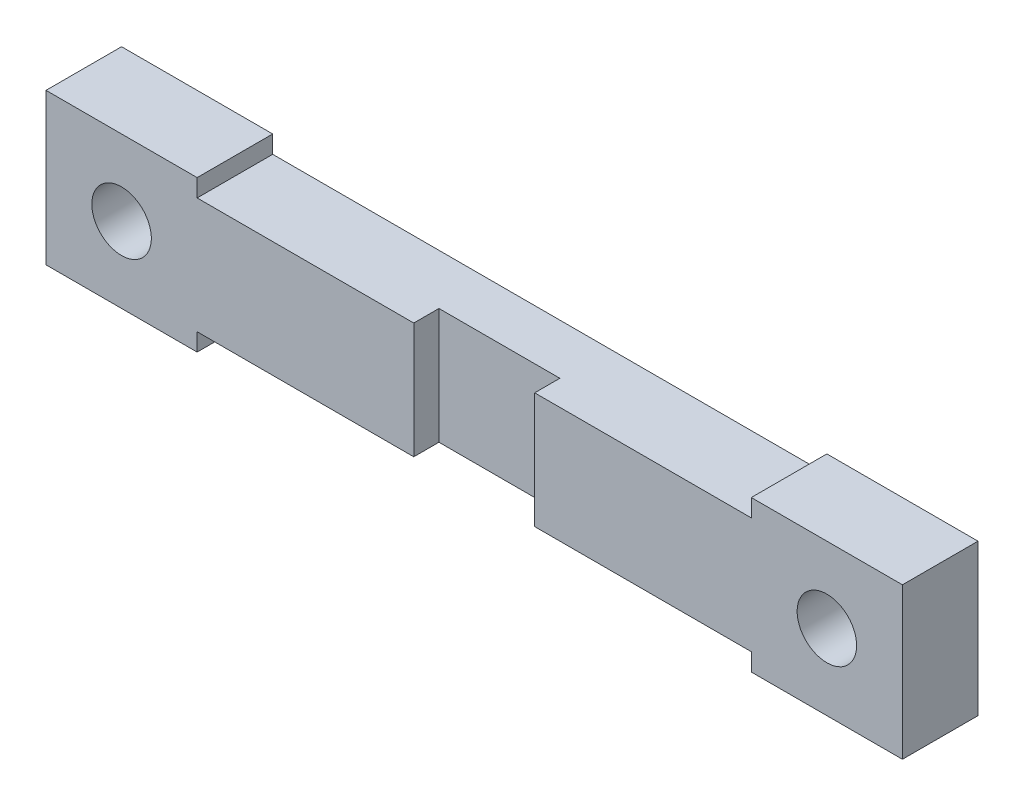
SolidWorks part; units mm, degrees
ref_plane "Front Plane" through (0, 0, 0) normal (0, 0, 1) x (1, 0, 0)
ref_plane "Top Plane" through (0, 0, 0) normal (0, 1, 0) x (1, 0, 0)
ref_plane "Right Plane" through (0, 0, 0) normal (1, 0, 0) x (0, 0, -1)
sketch "Sketch1" plane through (0, 0, 0) normal (0, 0, 1) x (1, 0, 0)
  line L0 (0, 2.921) -> (0, -2.921) construction
  line L1 (-13.97, -2.921) -> (13.97, -2.921)
  line L2 (-13.97, -2.921) -> (-13.97, 2.921)
  line L3 (-13.97, 2.921) -> (13.97, 2.921)
  line L4 (13.97, -2.921) -> (13.97, 2.921)
  line L5 (-13.97, -2.921) -> (13.97, 2.921) construction
  line L6 (-13.97, 2.921) -> (13.97, -2.921) construction
  line L7 (21.59, 0) -> (13.97, 0) construction
  line L8 (13.97, 3.81) -> (21.59, 3.81)
  line L9 (13.97, 3.81) -> (13.97, -3.81)
  line L10 (13.97, -3.81) -> (21.59, -3.81)
  line L11 (21.59, 3.81) -> (21.59, -3.81)
  line L12 (-13.97, -3.81) -> (-21.59, -3.81)
  line L13 (-21.59, 3.81) -> (-21.59, -3.81)
  line L14 (-13.97, 3.81) -> (-21.59, 3.81)
  line L15 (-13.97, 3.81) -> (-13.97, -3.81)
  circle A0 centre (17.78, 0) radius 1.5
  circle A1 centre (-17.78, 0) radius 1.5
  circle A2 centre (0, 0) radius 17.78 construction
  point P0 (0, 0)
  point P24 (17.78, 0)
  point P25 (20.6185, 4.1614)
  dimension "D1" = 3
  dimension "D2" = 35.56
  dimension "D3" = 3.81
  dimension "D4" = 3.81
  dimension "D5" = 5.842
extrude "Boss-Extrude1" add sketch "Sketch1" along normal blind 3.81 contours L15 L14 L13 L12 L2 A1 | L1 L4 L3 L2 | L11 L8 L9 L4 L10 A0 region at (0, 0, 0) region at (-14.0778, -3.3655, 0) region at (14.0778, 0, 0)
sketch "Sketch2" plane through (0, 0, 3.81) normal (0, 0, 1) x (1, 0, 0)
  line L0 (-13.97, 2.921) -> (13.97, 2.921) construction
  line L1 (-3.048, -2.921) -> (3.048, -2.921)
  line L2 (-3.048, -2.921) -> (-3.048, 2.921)
  line L3 (-3.048, 2.921) -> (3.048, 2.921)
  line L4 (3.048, -2.921) -> (3.048, 2.921)
  line L5 (-3.048, -2.921) -> (3.048, 2.921) construction
  line L6 (-3.048, 2.921) -> (3.048, -2.921) construction
  point P0 (0, 0)
  dimension "D1" = 6.096
extrude "Cut-Extrude1" cut sketch "Sketch2" against normal blind 1.27
